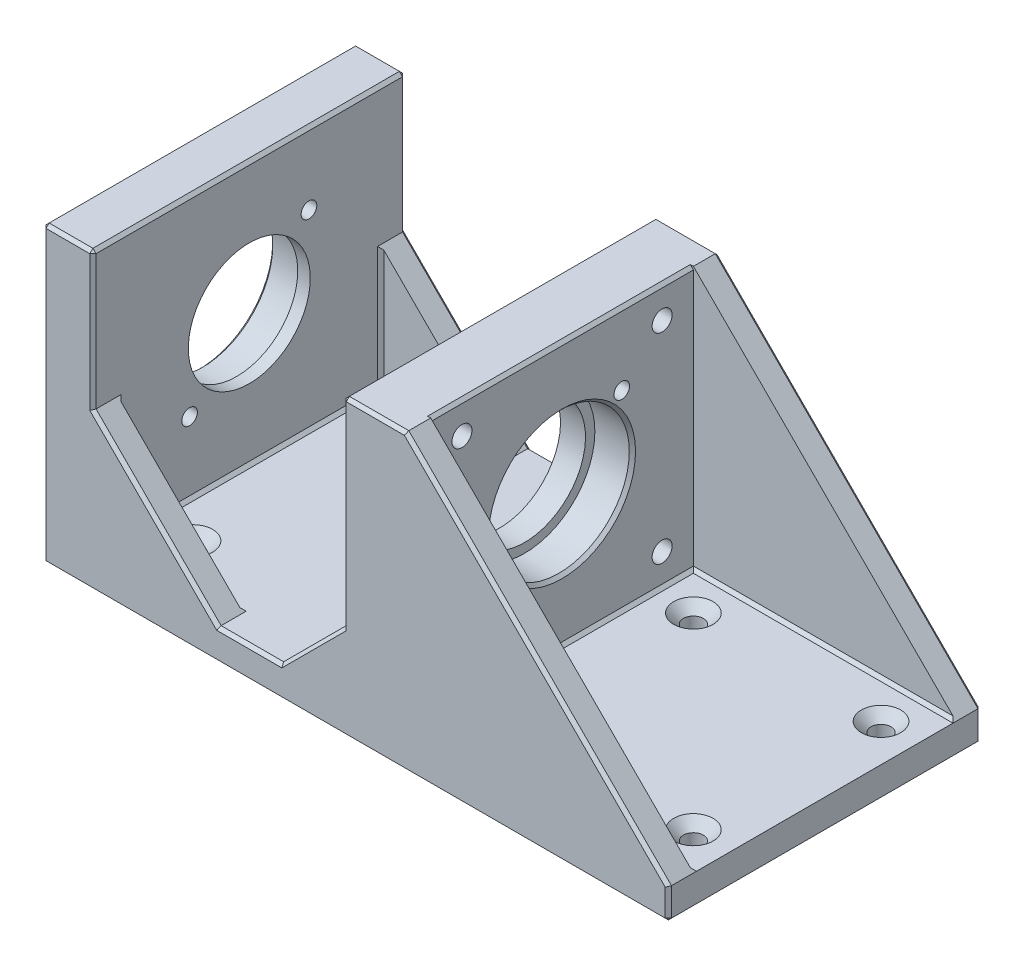
SolidWorks part; units mm, degrees
ref_plane "Front Plane" through (0, 0, 0) normal (0, 0, 1) x (1, 0, 0)
ref_plane "Top Plane" through (0, 0, 0) normal (0, 1, 0) x (1, 0, 0)
ref_plane "Right Plane" through (0, 0, 0) normal (1, 0, 0) x (0, 0, -1)
sketch "Sketch1" plane through (0, 0, 0) normal (0, 0, 1) x (1, 0, 0)
  line L0 (-10, 21) -> (-10, -11)
  line L1 (-20, -21) -> (-30, -21)
  line L2 (-50, -1) -> (-50, 21)
  line L3 (-50, 21) -> (-58, 21)
  line L4 (-58, 21) -> (-58, -26)
  line L5 (-58, -26) -> (42, -26)
  line L6 (42, -26) -> (42, -21)
  line L8 (42, -21) -> (0, 21)
  line L9 (0, 21) -> (-10, 21)
  line L10 (-30, -21) -> (-50, -1)
  line L11 (-10, -11) -> (-20, -21)
  point P1 (-10, -21)
  point P3 (-50, -21)
  dimension "D1" = 42
  dimension "D2" = 40
  dimension "D3" = 5
  dimension "D4" = 8
  dimension "D5" = 10
  dimension "D6" = 45
  dimension "D7" = 21
extrude "Boss-Extrude1" add sketch "Sketch1" along normal mid plane 50
sketch "Sketch2" plane through (0, 0, 0) normal (0, 0, 1) x (1, 0, 0)
  line L0 (-50, 21) -> (-50, -21)
  line L1 (-50, -21) -> (-10, -21)
  line L2 (-10, -21) -> (-10, 21)
  line L3 (-20, -21) -> (-30, -21) construction
  line L4 (-10, 21) -> (-50, 21)
  line L5 (0, 21) -> (0, -21)
  line L6 (0, -21) -> (42, -21)
  line L7 (42, -21) -> (0, 21)
extrude "Cut-Extrude1" cut sketch "Sketch2" along normal offset from surface 4 and the other way offset from surface 4 up to face at (-18.3636, -3.9091, 25) other way up to face at (-18.3636, -3.9091, -25)
sketch "Sketch3" plane through (0, 0, 0) normal (1, 0, 0) x (0, 0, -1)
  circle A0 centre (0, 0) radius 11.25
  dimension "D1" = 22.5
extrude "Cut-Extrude2" cut sketch "Sketch3" against normal through all both and the other way through all
sketch "Sketch4" plane through (-50, 0, 0) normal (-1, 0, 0) x (0, 0, 1)
  circle A1 centre (0, 0) radius 11.25 construction
  circle A2 centre (0, 0) radius 9.75
  circle A3 centre (0, 0) radius 9.75
  circle A4 centre (0, 0) radius 11.25
  dimension "D1" = 1.5
extrude "Boss-Extrude2" add sketch "Sketch4" along normal blind 2
hole_wizard "Tap Drill for M3x0.5 Tap1" positions "Sketch8" profile "Sketch10" hole size "M3x0.5" standard "ANSI Metric" end condition through all
sketch "Sketch8" plane through (-58, 0, 0) normal (-1, 0, 0) x (0, 0, 1)
  line L0 (-9.5459, 9.5459) -> (9.5459, -9.5459)
  line L2 (25, 21) -> (-25, 21) construction
  point P0 (-9.5459, 9.5459)
  point P2 (9.5459, -9.5459)
  point P11 (0, 0)
  dimension "D1" = 45
  dimension "D2" = 27
sketch "Sketch10" plane through (-58, 9.5459, -9.5459) normal (0, 1, 0) x (0, 0, 1)
  line L0 (0, 0) -> (0, 100)
  line L1 (0, 100) -> (1.25, 100)
  line L2 (1.25, 100) -> (1.25, 0)
  line L5 (1.25, 0) -> (0, 0)
  line L11 (0, -6.35) -> (0, 107.95) construction
  dimension "Thru Hole Dia." = 2.5
  dimension "Thru Hole Depth" = 100
hole_wizard "CSK for M3 Flat Head Machine Screw1" positions "Sketch12" profile "Sketch13" countersink size "M3" standard "ANSI Metric" end condition up to next
sketch "Sketch12" plane through (-10, 0, 0) normal (-1, 0, 0) x (0, 0, 1)
  line L1 (16, -16) -> (-16, -16) construction
  line L2 (16, -16) -> (16, 16) construction
  line L3 (16, 16) -> (-16, 16) construction
  line L4 (-16, -16) -> (-16, 16) construction
  line L5 (16, -16) -> (-16, 16) construction
  line L6 (16, 16) -> (-16, -16) construction
  point P0 (-16, 16)
  point P2 (16, 16)
  point P4 (16, -16)
  point P6 (-16, -16)
  point P9 (0, 0)
  dimension "D1" = 32
sketch "Sketch13" plane through (-10, 16, -16) normal (0, 1, 0) x (0, 0, 1)
  line L0 (0, 0) -> (0, 10)
  line L1 (0, 10) -> (1.6, 10)
  line L2 (1.6, 10) -> (1.6, 1.55)
  line L3 (1.6, 1.55) -> (3.15, 0)
  line L5 (3.15, 0) -> (0, 0)
  line L6 (-1.6, 1.55) -> (-3.15, 0) construction
  line L11 (0, -6.35) -> (0, 107.95) construction
  dimension "Thru Hole Dia." = 3.2
  dimension "Thru Hole Depth" = 10
  dimension "Near C'Sink Dia." = 6.3
  dimension "Near C'Sink Angle" = 90
hole_wizard "CSK for M3 Flat Head Machine Screw2" positions "Sketch14" profile "Sketch15" countersink size "M3" standard "ANSI Metric" end condition up to next
sketch "Sketch14" plane through (0, -21, 0) normal (0, 1, 0) x (1, 0, 0)
  line L0 (-10, -21) -> (-10, 21) construction
  line L2 (-30, 21) -> (-50, 21) construction
  line L3 (-30, -21) -> (-50, -21) construction
  line L4 (-50, -21) -> (-50, 21) construction
  line L5 (0, -21) -> (0, 21) construction
  line L7 (42, -21) -> (42, 21) construction
  point P0 (-44, 15)
  point P2 (-16, 15)
  point P4 (36, 15)
  point P6 (36, -15)
  point P8 (-16, -15)
  point P10 (-44, -15)
  point P12 (6, -15)
  point P14 (6, 15)
  dimension "D1" = 6
  dimension "D2" = 6
  dimension "D3" = 6
  dimension "D4" = 6
  dimension "D5" = 6
  dimension "D6" = 6
sketch "Sketch15" plane through (-44, -21, -15) normal (1, 0, 0) x (0, 0, 1)
  line L0 (0, 0) -> (0, 5)
  line L1 (0, 5) -> (1.6, 5)
  line L2 (1.6, 5) -> (1.6, 1.55)
  line L3 (1.6, 1.55) -> (3.15, 0)
  line L5 (3.15, 0) -> (0, 0)
  line L6 (-1.6, 1.55) -> (-3.15, 0) construction
  line L11 (0, -6.35) -> (0, 107.95) construction
  dimension "Thru Hole Dia." = 3.2
  dimension "Thru Hole Depth" = 5
  dimension "Near C'Sink Dia." = 6.3
  dimension "Near C'Sink Angle" = 90
chamfer "Chamfer1" distance 0.5 angle 45 43 edges at (0, 0, -11.25) (-58, 0, -11.25) (-10, -16, -21) (-10, -16, 21) (-15, -21, 21) (-10, -21, 0) (-15, -21, -21) (-50, -11, 21) (-50, -11, -21) (-40, -21, -21) (-50, -21, 0) (-40, -21, 21) (21, -21, 21) (0, -21, 0) (21, -21, -21) (0, 21, 0) (-10, 21, 0) (-5, 21, 25) (-10, 5, 25) (-15, -16, 25) (-25, -21, 25) (-40, -11, 25) (-50, 10, 25) (-54, 21, 25) (-50, 21, 0) (-58, 21, 0) (-54, 21, -25) (-50, 10, -25) (-40, -11, -25) (-25, -21, -25) (-15, -16, -25) (-10, 5, -25) (-5, 21, -25) (21, 0, 25) (21, 0, -25) (42, -23.5, 25) (42, -23.5, -25) (-58, -2.5, -25) (-58, -2.5, 25) (42, -26, 0) (-8, -26, -25) (-58, -26, 0) (-8, -26, 25)
extrude "Boss-Extrude3" add sketch "Sketch4<2>" against normal blind 4 from surface starting at face at (-10, -5.5, 0)
sketch "Sketch4<2>" plane through (-50, 0, 0) normal (-1, 0, 0) x (0, 0, 1) same geometry as "Sketch4"
